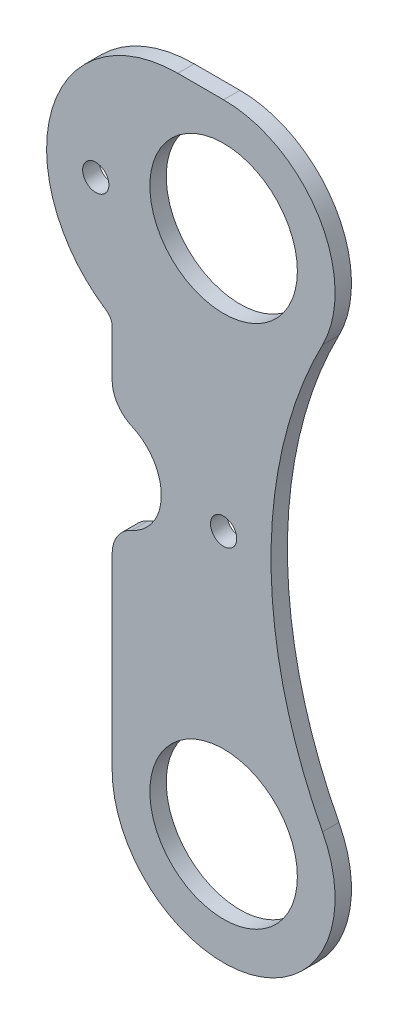
SolidWorks part; units mm, degrees
material "6061 Alloy"
ref_plane "Front Plane" through (0, 0, 0) normal (0, 0, 1) x (1, 0, 0)
ref_plane "Top Plane" through (0, 0, 0) normal (0, 1, 0) x (1, 0, 0)
ref_plane "Right Plane" through (0, 0, 0) normal (1, 0, 0) x (0, 0, -1)
sketch "Sketch1" plane through (0, 0, 0) normal (0, 0, 1) x (1, 0, 0)
  line L0 (0, 0) -> (0, -101.6) construction
  line L1 (21.59, -120.5575) -> (-21.59, -120.5575) construction
  line L2 (-8.89, 25.4) -> (8.89, 25.4)
  line L3 (-21.59, 12.7) -> (-21.59, -117.7751)
  line L5 (21.59, 12.7) -> (21.59, -117.7751)
  line L9 (-23.3829, -122.6853) -> (-33.2033, -134.3394)
  line L10 (-36.322, 25.4) -> (20.828, 25.4) construction
  line L11 (-36.322, 25.4) -> (-36.322, -203.2) construction
  line L12 (-36.322, -203.2) -> (20.828, -203.2) construction
  line L13 (20.828, 25.4) -> (20.828, -203.2) construction
  line L15 (-7.9527, -155.6168) -> (19.7971, -122.6853)
  line L16 (-32.4392, -143.2871) -> (-16.9004, -156.3809)
  circle A0 centre (0, 0) radius 38.1 construction
  circle A1 centre (0, -101.6) radius 38.1 construction
  circle A2 centre (0, 0) radius 14.2875
  circle A3 centre (0, -101.6) radius 14.2875
  arc A6 (8.89, 25.4) -> (21.59, 12.7) centre (8.89, 12.7) cw
  arc A7 (-8.89, 25.4) -> (-21.59, 12.7) centre (-8.89, 12.7) ccw
  circle A10 centre (-18.5321, -142.5501) radius 2.54
  arc A13 (-23.3829, -122.6853) -> (-21.59, -117.7751) centre (-29.21, -117.7751) ccw
  arc A14 (19.7971, -122.6853) -> (21.59, -117.7751) centre (13.97, -117.7751) ccw
  arc A15 (-16.9004, -156.3809) -> (-7.9527, -155.6168) centre (-12.8086, -151.525) ccw
  arc A16 (-33.2033, -134.3394) -> (-32.4392, -143.2871) centre (-28.3474, -138.4312) ccw
  circle A17 centre (0, -50.8) radius 2.54
  point P13 (-192.705, 39.2708)
  point P20 (21.59, 25.4)
  point P23 (-21.59, 25.4)
  point P31 (-36.322, -138.0404)
  dimension "D2" = 76.2
  dimension "D3" = 76.2
  dimension "D4" = 28.575
  dimension "D5" = 28.575
  dimension "D10" = 228.6
  dimension "D11" = 36.322
  dimension "D13" = 5.08
  dimension "D19" = 6.35
  dimension "D20" = 7.62
  dimension "D21" = 12.7
  dimension "D22" = 5.08
  dimension "D1" = 101.6
  dimension "D6" = 43.18
  dimension "D7" = 21.59
  dimension "D8" = 25.4
  dimension "D9" = 57.15
  dimension "D12" = 25.4
  dimension "D14" = 33.02
  dimension "D15" = 16.51
  dimension "D16" = 21.59
  dimension "D17" = 9.525
  dimension "D18" = 18.9575
extrude "Boss-Extrude1" add sketch "Sketch1" along normal blind 3.175
sketch "Sketch2" plane through (0, 0, 0) normal (0, 0, 1) x (1, 0, 0)
  line L0 (-21.59, -41.275) -> (-21.59, -60.325)
  line L1 (0, 0) -> (0, -101.6) construction
  line L4 (21.59, -117.7751) -> (21.59, 12.7) construction
  line L5 (-21.59, -50.8) -> (97.79, -50.8) construction
  line L6 (-21.59, 12.7) -> (-21.59, -117.7751) construction
  line L7 (0, 0) -> (-39.9512, 0) construction
  line L9 (16.51, -115.5122) -> (-17.5013, -155.8745)
  line L10 (-32.4392, -143.2871) -> (-16.9004, -156.3809) construction
  line L11 (-7.9527, -155.6168) -> (19.7971, -122.6853) construction
  line L13 (27.94, -121.6567) -> (-7.6203, -163.8572)
  line L14 (-7.6203, -163.8572) -> (-17.5013, -155.8745)
  line L15 (27.94, -121.6567) -> (27.94, 0)
  line L16 (27.94, 0) -> (21.59, 0)
  arc A1 (19.1591, -91.6472) -> (19.1591, -9.9528) centre (97.79, -50.8) cw
  arc A2 (-21.59, -60.325) -> (-21.59, -41.275) centre (-21.59, -50.8) ccw
  arc A3 (21.59, 0) -> (19.1591, -9.9528) centre (0, 0) cw
  arc A4 (21.59, -101.6) -> (19.1591, -91.6472) centre (0, -101.6) ccw
  arc A5 (21.59, -101.6) -> (16.51, -115.5122) centre (0, -101.6) cw
  dimension "D2" = 12.7
  dimension "D3" = 50.8
  dimension "D4" = 6.35
  dimension "D1" = 76.2
  dimension "D5" = 19.05
extrude "Cut-Extrude1" cut sketch "Sketch2" along normal through all contours A1 A3 L16 L15 L13 L14 L9 A5 A4 | L0 A2
sketch "Sketch3" plane through (0, 0, 3.175) normal (0, 0, 1) x (1, 0, 0)
  line L0 (-27.3514, -127.3948) -> (-36.0255, -137.6886)
  line L3 (-27.3514, -127.3948) -> (-7.5576, -144.074)
  line L4 (-23.3829, -122.6853) -> (-33.2033, -134.3394) construction
  line L5 (16.51, -115.5122) -> (-17.5013, -155.8745) construction
  line L7 (-35.4064, -144.9387) -> (-24.4031, -154.2106)
  line L8 (-23.3829, -122.6853) -> (-33.2033, -134.3394) construction
  line L9 (-7.5576, -144.074) -> (-15.4554, -153.4465)
  line L10 (-32.4392, -143.2871) -> (-17.5013, -155.8745) construction
  circle A2 centre (-18.5321, -142.5501) radius 2.54
  circle A3 centre (-18.5321, -142.5501) radius 2.54 construction
  arc A5 (-36.0255, -137.6886) -> (-35.4064, -144.9387) centre (-32.0909, -141.0041) ccw
  arc A6 (-24.4031, -154.2106) -> (-15.4554, -153.4465) centre (-20.3113, -149.3547) ccw
  dimension "D2" = 6.35
  dimension "D3" = 5.1453
  dimension "D1" = 3.175
fillet "Fillet3" radius 6.35 2 edges at (-21.59, -41.275, 1.5875) (-21.59, -60.325, 1.5875)
extrude "Boss-Extrude3" add sketch "Sketch3" against normal blind 3.175
sketch "Sketch6" plane through (0, 0, 3.175) normal (0, 0, 1) x (1, 0, 0)
  line L0 (-35.4064, -144.9387) -> (-63.6204, -121.1641)
  line L1 (-63.6204, -121.1641) -> (-51.345, -106.5965)
  line L2 (-51.345, -106.5965) -> (-27.0656, -127.0555)
  line L4 (-35.4064, -144.9387) -> (-24.4031, -154.2106) construction
  line L5 (-23.3829, -122.6853) -> (-36.0255, -137.6886) construction
  line L6 (-35.4064, -144.9387) -> (-27.0656, -127.0555)
  circle A0 centre (-52.6268, -117.9721) radius 2.54
  dimension "D4" = 5.08
  dimension "D1" = 31.75
  dimension "D2" = 9.525
  dimension "1" = 19.05
  dimension "D3" = 6.35
extrude "Boss-Extrude4" add sketch "Sketch6" against normal blind 3.175
fillet "Fillet2" radius 6.35 3 edges at (-63.6204, -121.1641, 1.5875) (-51.345, -106.5965, 1.5875) (-27.0656, -127.0555, 1.5875)
sketch "Sketch7" plane through (0, 0, 3.175) normal (0, 0, 1) x (1, 0, 0)
  line L0 (-21.59, 12.7) -> (-21.59, -36.2503) construction
  line L1 (21.59, 0) -> (21.59, 12.7) construction
  line L2 (-21.59, 0) -> (21.59, 0) construction
  line L3 (-21.59, 0) -> (-21.59, 31.75)
  line L4 (-21.59, 31.75) -> (21.59, 31.75)
  line L5 (21.59, 31.75) -> (21.59, 0)
  line L6 (8.89, 25.4) -> (-8.89, 25.4) construction
  arc A0 (-21.59, 0) -> (21.59, 0) centre (0, 0) cw
  dimension "D1" = 6.35
extrude "Cut-Extrude2" cut sketch "Sketch7" against normal through all
sketch "Sketch10" plane through (0, 0, 3.175) normal (0, 0, 1) x (1, 0, 0)
  line L0 (16.51, -115.5122) -> (-17.5013, -155.8745) construction
  line L1 (-18.1519, -155.3263) -> (-17.3615, -157.512)
  line L2 (-17.3615, -157.512) -> (-14.3757, -156.4323)
  line L3 (-14.3757, -156.4323) -> (-15.4554, -153.4465)
  line L5 (-18.1519, -155.3263) -> (-17.5013, -155.8745) construction
  circle A0 centre (-20.3113, -149.3547) radius 6.35 construction
  arc A1 (-24.4031, -154.2106) -> (-18.1519, -155.3263) centre (-20.3113, -149.3547) ccw construction
  arc A2 (-18.1519, -155.3263) -> (-15.4554, -153.4465) centre (-20.3113, -149.3547) ccw
  dimension "D1" = 3.175
  dimension "D2" = 30
extrude "Cut-Extrude3" cut sketch "Sketch10" against normal through all
sketch "Sketch12" plane through (0, 0, 3.175) normal (0, 0, 1) x (1, 0, 0)
  line L0 (-21.59, -65.3497) -> (-21.59, -117.7751) construction
  line L1 (-21.59, -101.6) -> (-72.39, -101.6)
  line L2 (-72.39, -101.6) -> (-72.39, -165.1)
  line L3 (-72.39, -165.1) -> (16.51, -165.1)
  line L4 (16.51, -165.1) -> (16.51, -115.5122)
  arc A2 (16.51, -115.5122) -> (-21.59, -101.6) centre (0, -101.6) cw
  dimension "D1" = 63.5
  dimension "D2" = 88.9
extrude "Cut-Extrude4" cut sketch "Sketch12" against normal through all
sketch "Sketch15" plane through (0, 0, 3.175) normal (0, 0, 1) x (1, 0, 0)
  line L0 (-21.59, 0) -> (-21.59, -36.2503) construction
  line L5 (-21.59, -29.21) -> (-21.59, 0)
  line L7 (0, 21.59) -> (-16.6076, 6.9565)
  line L8 (-16.6076, 6.9565) -> (-12.5785, -28.9408)
  line L9 (-8.89, 21.59) -> (0, 21.59)
  arc A0 (-12.5785, -28.9408) -> (-34.29, -3.81) centre (-8.89, -3.81) cw
  arc A1 (-8.89, 21.59) -> (-34.29, -3.81) centre (-8.89, -3.81) ccw
  circle A2 centre (-24.765, -3.81) radius 2.54
  arc A3 (19.1591, -9.9528) -> (-21.59, 0) centre (0, 0) ccw construction
  arc M10 (19.1591, -9.9528) -> (-21.59, 0) centre (0, 0) ccw
  line M11 (-21.59, 0) -> (-21.59, -36.2503)
  dimension "D1" = 12.7
  dimension "D4" = 3.175
  dimension "D3" = 5.08
  dimension "D2" = 25.4
extrude "Boss-Extrude8" add sketch "Sketch15" against normal blind 3.175 contours L9 A1 A0 A2 M11 M10 region at (-24.9677, -0.0937, 3.175)
fillet "Fillet4" radius 2.54 1 edges at (-21.59, -25.807, 1.5875)
